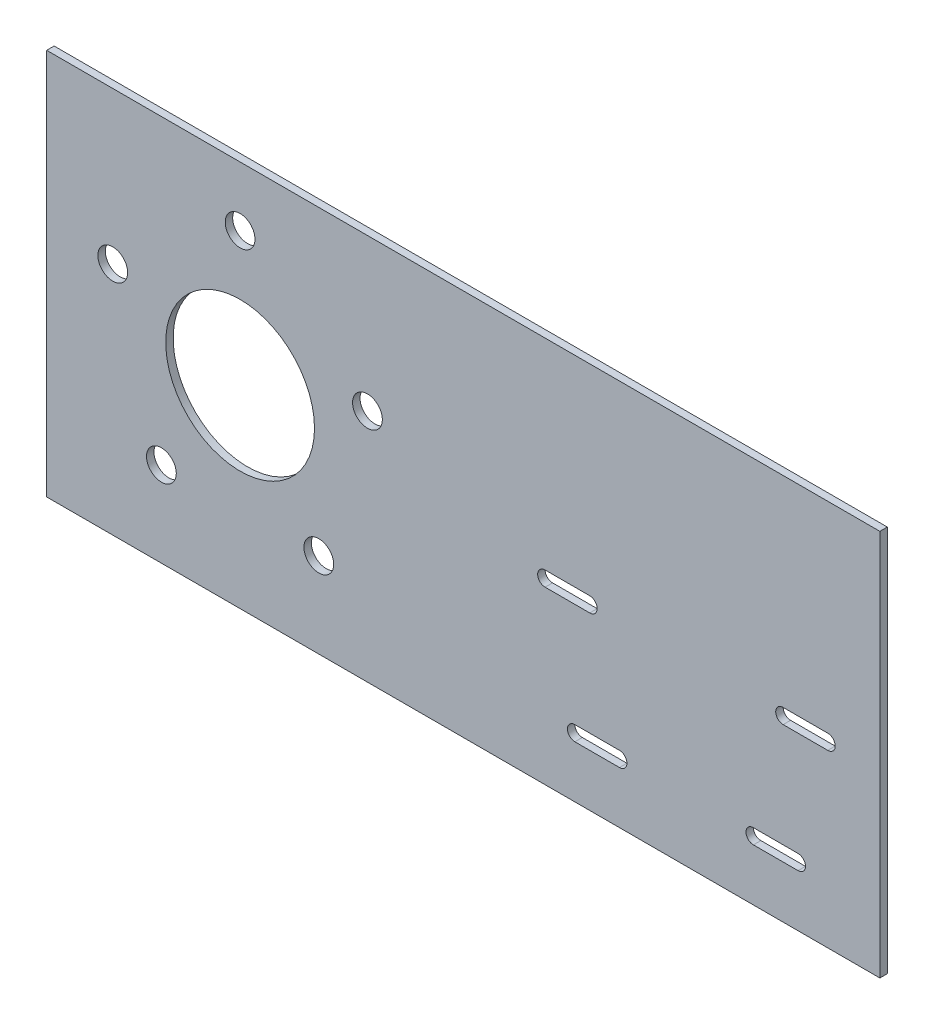
SolidWorks part; units mm, degrees
material "ASTM A36 Steel"
ref_plane "Front Plane" through (0, 0, 0) normal (0, 0, 1) x (1, 0, 0)
ref_plane "Top Plane" through (0, 0, 0) normal (0, 1, 0) x (1, 0, 0)
ref_plane "Right Plane" through (0, 0, 0) normal (1, 0, 0) x (0, 0, -1)
ref_plane "Plane1" through (190.5, 0, 0) normal (1, 0, 0) x (0, 0, -1)
sketch "Sketch1" [suppressed] plane through (0, 0, 0) normal (0, 0, 1) x (1, 0, 0)
  circle A2 centre (0, 0) radius 80.645
  circle A9 centre (-33.3856, -45.9513) radius 6.35
  circle A10 centre (33.3856, -45.9513) radius 6.35
  circle A11 centre (54.019, 17.5518) radius 6.35
  circle A12 centre (0, 56.7989) radius 6.35
  circle A13 centre (-54.019, 17.5518) radius 6.35
  point P1 (0, 0)
sketch "Sketch2" plane through (0, 0, 0) normal (0, 0, 1) x (1, 0, 0)
  line L0 (88.7095, 0) -> (-88.7095, 0) construction
  line L1 (273.05, -82.55) -> (-82.55, -82.55)
  line L2 (273.05, -82.55) -> (273.05, 82.55)
  line L3 (273.05, 82.55) -> (-82.55, 82.55)
  line L4 (-82.55, -82.55) -> (-82.55, 82.55)
  line L5 (273.05, -82.55) -> (-82.55, 82.55) construction
  line L6 (273.05, 82.55) -> (-82.55, -82.55) construction
  line L7 (0, -88.7095) -> (0, 88.7095) construction
  circle A0 centre (0, 0) radius 31.75
  circle A6 centre (0, 57.15) radius 6.35
  circle A11 centre (0, 0) radius 57.15 construction
  point P18 (95.25, 0)
  dimension "D1" = 63.5
  dimension "D5" = 114.3
  dimension "D6" = 12.7
  dimension "D2" = 165.1
  dimension "D3" = 82.55
  dimension "D4" = 355.6
extrude "Boss-Extrude1" add sketch "Sketch2" along normal blind 3.175
sketch "Sketch3" plane through (0, 0, 3.175) normal (0, 0, 1) x (1, 0, 0)
  line L0 (190.5, -88.7095) -> (190.5, 88.7095) construction
  line L1 (139.7, -6.35) -> (241.3, -6.35) construction
  line L2 (190.5, -6.35) -> (190.5, -57.15) construction
  line L3 (152.4, -57.15) -> (228.6, -57.15) construction
  line L4 (149.225, -6.35) -> (130.175, -6.35) construction
  line L5 (139.7, -6.35) -> (228.6, -57.15) construction
  line L6 (152.4, -57.15) -> (241.3, -6.35) construction
  line L7 (149.225, -9.525) -> (130.175, -9.525)
  line L8 (149.225, -3.175) -> (130.175, -3.175)
  line L9 (250.825, -6.35) -> (231.775, -6.35) construction
  line L10 (250.825, -9.525) -> (231.775, -9.525)
  line L11 (250.825, -3.175) -> (231.775, -3.175)
  line L12 (238.125, -57.15) -> (219.075, -57.15) construction
  line L13 (238.125, -60.325) -> (219.075, -60.325)
  line L14 (238.125, -53.975) -> (219.075, -53.975)
  line L15 (142.875, -57.15) -> (161.925, -57.15) construction
  line L16 (142.875, -53.975) -> (161.925, -53.975)
  line L17 (142.875, -60.325) -> (161.925, -60.325)
  line L18 (273.05, 82.55) -> (-82.55, 82.55) construction
  arc A0 (149.225, -9.525) -> (149.225, -3.175) centre (149.225, -6.35) ccw
  arc A1 (130.175, -3.175) -> (130.175, -9.525) centre (130.175, -6.35) ccw
  arc A2 (250.825, -9.525) -> (250.825, -3.175) centre (250.825, -6.35) ccw
  arc A3 (231.775, -3.175) -> (231.775, -9.525) centre (231.775, -6.35) ccw
  arc A4 (238.125, -60.325) -> (238.125, -53.975) centre (238.125, -57.15) ccw
  arc A5 (219.075, -53.975) -> (219.075, -60.325) centre (219.075, -57.15) ccw
  arc A6 (142.875, -53.975) -> (142.875, -60.325) centre (142.875, -57.15) ccw
  arc A7 (161.925, -60.325) -> (161.925, -53.975) centre (161.925, -57.15) ccw
  point P0 (190.5, -35.3786)
  point P11 (139.7, -6.35)
  point P18 (241.3, -6.35)
  point P23 (228.6, -57.15)
  point P30 (152.4, -57.15)
  dimension "D1" = 50.8
  dimension "D2" = 101.6
  dimension "D3" = 76.2
  dimension "D4" = 88.9
  dimension "D5" = 19.05
  dimension "D6" = 6.35
extrude "Cut-Extrude1" cut sketch "Sketch3" against normal through all
ref_plane "Plane2" through (0, -6.35, 0) normal (0, 1, 0) x (-1, 0, 0)
sketch "Sketch4" [suppressed] plane through (0, 0, 3.175) normal (0, 0, 1) x (1, 0, 0)
  line L0 (241.3, 57.15) -> (112.395, 57.15)
  line L1 (106.045, 50.8) -> (106.045, 28.575)
  line L2 (112.395, 22.225) -> (241.3, 22.225)
  line L3 (247.65, 28.575) -> (247.65, 50.8)
  line L4 (273.05, 82.55) -> (-82.55, 82.55) construction
  line L5 (273.05, -82.55) -> (273.05, 82.55) construction
  line L6 (149.225, -3.175) -> (130.175, -3.175) construction
  arc A0 (112.395, 57.15) -> (106.045, 50.8) centre (112.395, 50.8) ccw
  arc A1 (106.045, 28.575) -> (112.395, 22.225) centre (112.395, 28.575) ccw
  arc A2 (241.3, 22.225) -> (247.65, 28.575) centre (241.3, 28.575) ccw
  arc A3 (247.65, 50.8) -> (241.3, 57.15) centre (241.3, 50.8) ccw
  circle A5 centre (0, 0) radius 80.645 construction
  circle A6 centre (0, 0) radius 80.645
  point P21 (80.645, 0)
  dimension "D4" = 6.35
  dimension "D1" = 25.4
  dimension "D2" = 25.4
  dimension "D3" = 25.4
  dimension "D5" = 25.4
extrude "Cut-Extrude3" [suppressed] cut sketch "Sketch4" against normal through all contours L3 A3 L0 A0 L1 A1 L2 A2
sketch3d "TAG"
  line L0 (273.05, 82.55, 0) -> (-82.55, 82.55, 0) construction
  line L1 (273.05, 82.55, 3.175) -> (273.05, 82.55, 0) construction
  line L2 (273.05, -82.55, 0) -> (273.05, 82.55, 0) construction
  line L3 (273.05, 82.55, 0) -> (-82.55, 82.55, 0)
  line L4 (273.05, 82.55, 3.175) -> (273.05, 82.55, 0)
  line L5 (273.05, -82.55, 0) -> (273.05, 82.55, 0)
  dimension "D1" = 3.175
  dimension "D2" = 165.1
  dimension "D3" = 355.6
pattern_circular "CirPattern1" count 5 over 360 about axis through (0, 0, 3.175) along (0, 0, -1) of face at (6.35, 57.15, 3.175)
